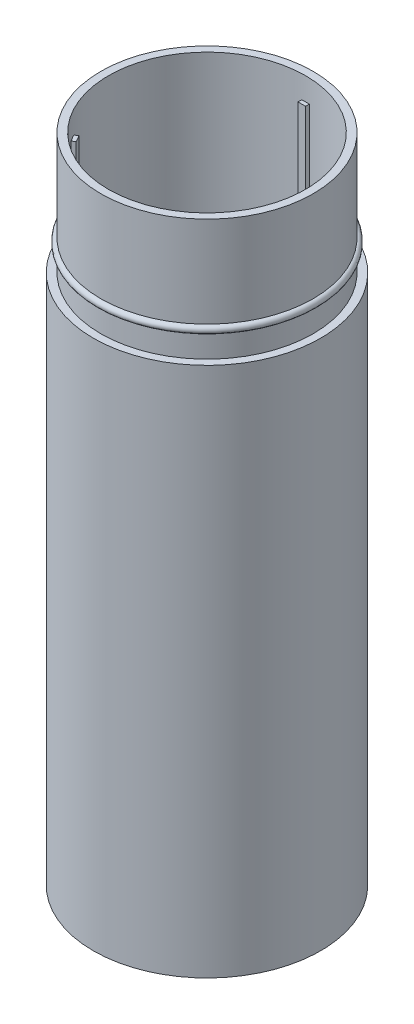
SolidWorks part; units mm, degrees
ref_plane "Front Plane" through (0, 0, 0) normal (0, 0, 1) x (1, 0, 0)
ref_plane "Top Plane" through (0, 0, 0) normal (0, 1, 0) x (1, 0, 0)
ref_plane "Right Plane" through (0, 0, 0) normal (1, 0, 0) x (0, 0, -1)
sketch "Sketch1" plane through (0, 0, 0) normal (0, 1, 0) x (1, 0, 0)
  circle A0 centre (0, 0) radius 15
  dimension "D1" = 30
extrude "Boss-Extrude1" add sketch "Sketch1" along normal blind 70
sketch "Sketch2" plane through (0, 70, 0) normal (0, 1, 0) x (1, 0, 0)
  circle A0 centre (0, 0) radius 14
  dimension "D1" = 28
extrude "Boss-Extrude2" add sketch "Sketch2" along normal blind 16
sketch "Sketch3" plane through (0, 0, 0) normal (0, 0, 1) x (1, 0, 0)
  line L0 (-14, 86) -> (-14, 70) construction
  line L3 (15, 70) -> (-15, 70) construction
  line L4 (0, 70) -> (0, 86) construction
  line L5 (14, 86) -> (-14, 86) construction
  circle A0 centre (-14, 73.5) radius 0.5
  dimension "D2" = 1
  dimension "D1" = 3.5
revolve "Revolve1" add sketch "Sketch3" angle 360 about L4
sketch "Sketch4" plane through (0, 86, 0) normal (0, 1, 0) x (1, 0, 0)
  circle A0 centre (0, 0) radius 13
  dimension "D1" = 26
extrude "Cut-Extrude1" cut sketch "Sketch4" against normal blind 78
sketch "Sketch5" plane through (0, 8, 0) normal (0, 1, 0) x (1, 0, 0)
  circle A0 centre (0, 0) radius 2
  dimension "D1" = 4
extrude "Cut-Extrude2" cut sketch "Sketch5" against normal through all
sketch "Sketch6" plane through (0, 8, 0) normal (0, 1, 0) x (1, 0, 0)
  line L1 (-0.5, 12.5) -> (0.5, 12.5)
  line L2 (-0.5, 12.5) -> (-0.5, 13.292)
  line L3 (-0.5, 13.292) -> (0.5, 13.292)
  line L4 (0.5, 12.5) -> (0.5, 13.292)
  circle A0 centre (0, 0) radius 13 construction
  dimension "D1" = 0.5
  dimension "D2" = 1
  dimension "D3" = 12.5
extrude "Boss-Extrude3" add sketch "Sketch6" along normal blind 75
pattern_circular "CirPattern1" count 3 over 360 about axis through (0, 86, 0) along (0, 1, 0) of "Boss-Extrude3"
sketch "Sketch7" plane through (0, 0, 0) normal (0, -1, 0) x (1, 0, 0)
  circle A0 centre (0, 0) radius 14
  dimension "D1" = 28
extrude "Cut-Extrude3" cut sketch "Sketch7" against normal blind 5
scale "Scale1" scale about origin uniform scaling yes scale factor 0.655
